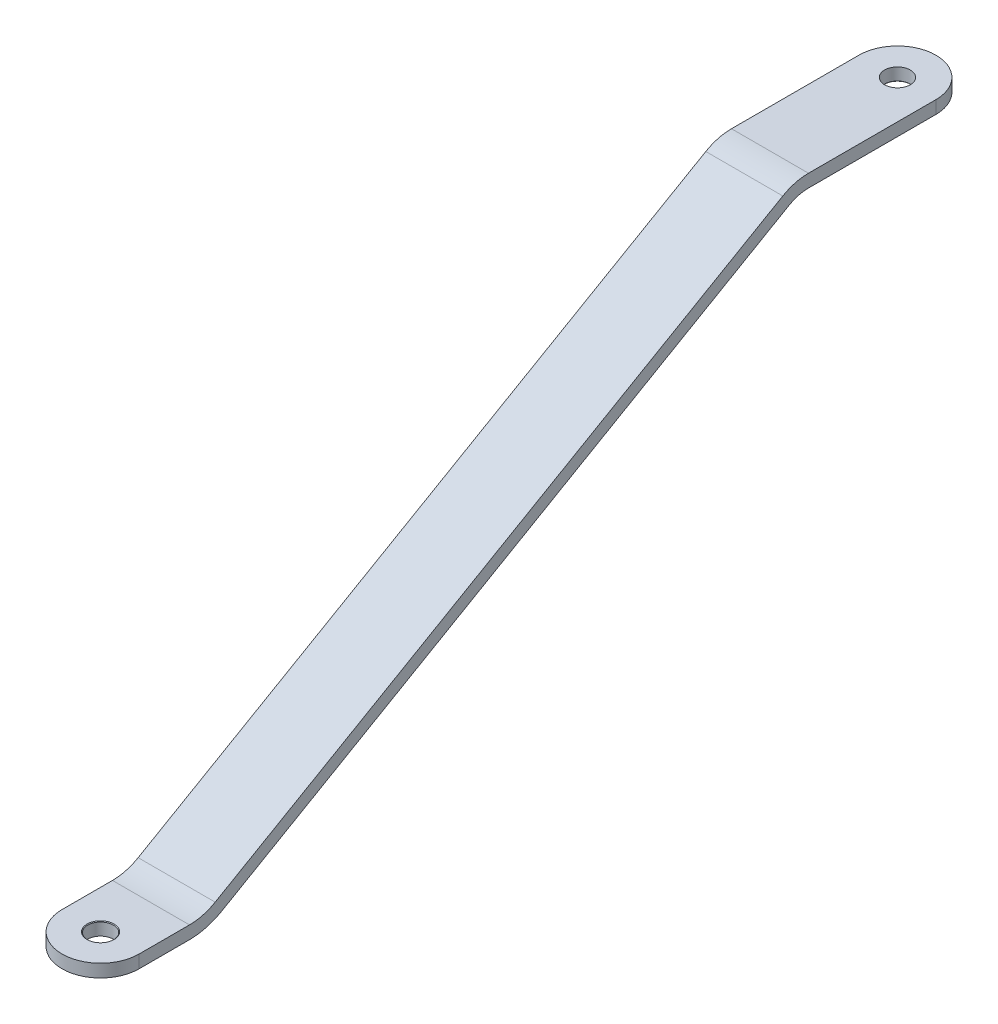
SolidWorks part; units mm, degrees
ref_plane "Front Plane" through (0, 0, 0) normal (0, 0, 1) x (1, 0, 0)
ref_plane "Top Plane" through (0, 0, 0) normal (0, 1, 0) x (1, 0, 0)
ref_plane "Right Plane" through (0, 0, 0) normal (1, 0, 0) x (0, 0, -1)
sketch "Sketch2" plane through (0, 0, 0) normal (1, 0, 0) x (0, 0, -1)
  line L0 (-394.1607, 0) -> (-306.1725, 0)
  line L1 (-280.7725, 6.8059) -> (280.7725, 331.0141)
  line L2 (306.1725, 337.82) -> (470.3607, 337.82)
  line L3 (0, 0) -> (470.3607, 0) construction
  line L4 (-394.1607, -12.7) -> (-306.1725, -12.7)
  line L5 (-274.4225, -4.1926) -> (287.1225, 320.0156)
  line L6 (306.1725, 325.12) -> (470.3607, 325.12)
  line L7 (-394.1607, 0) -> (-394.1607, -12.7)
  line L8 (470.3607, 337.82) -> (470.3607, 325.12)
  arc A0 (280.7725, 331.0141) -> (306.1725, 337.82) centre (306.1725, 287.02) cw
  arc A1 (-306.1725, 0) -> (-280.7725, 6.8059) centre (-306.1725, 50.8) ccw
  arc A2 (-306.1725, -12.7) -> (-274.4225, -4.1926) centre (-306.1725, 50.8) ccw
  arc A3 (287.1225, 320.0156) -> (306.1725, 325.12) centre (306.1725, 287.02) cw
  point P9 (0, 168.91)
  point P14 (292.5607, 337.82)
  point P17 (-292.5607, 0)
  dimension "D5" = 50.8
  dimension "D1" = 101.6
  dimension "D2" = 675.64
  dimension "D3" = 177.8
  dimension "D4" = 30
  dimension "D6" = 12.7
extrude "Boss-Extrude1" add sketch "Sketch2" along normal blind 76.2
fillet "Fillet1" 2 edges at (76.2, -6.35, 394.1607) (0, -6.35, 394.1607) type full round first side face at (76.2, 162.7739, -13.777) second side face at (0, 162.7739, -13.777) middle face at (38.1, -6.35, 394.1607)
fillet "Fillet2" 2 edges at (0, 331.47, -470.3607) (76.2, 331.47, -470.3607) type full round first side face at (0, 162.7739, -20.127) second side face at (76.2, 162.7739, -20.127) middle face at (38.1, 331.47, -470.3607)
hole_wizard "1 (1) Diameter Hole1" positions "Sketch3" profile "Sketch4" hole size "1" standard "ANSI Inch" end condition through all
sketch "Sketch3" plane through (0, 0, 0) normal (0, 1, 0) x (1, 0, 0)
  point P0 (38.1, -356.0607)
sketch "Sketch4" plane through (38.1, 0, 356.0607) normal (1, 0, 0) x (0, 0, 1)
  line L0 (0, 0) -> (0, 12.7)
  line L1 (0, 12.7) -> (12.7, 12.7)
  line L2 (12.7, 12.7) -> (12.7, 0.635)
  line L3 (12.7, 0.635) -> (13.335, 0)
  line L5 (13.335, 0) -> (0, 0)
  line L6 (-12.7, 0.635) -> (-13.335, 0) construction
  line L11 (0, -6.35) -> (0, 107.95) construction
  dimension "Thru Hole Dia." = 25.4
  dimension "Thru Hole Depth" = 12.7
  dimension "Near C'Sink Dia." = 26.67
  dimension "Near C'Sink Angle" = 90
hole_wizard "1 (1) Diameter Hole2" positions "3DSketch1" profile "Sketch7" hole size "1" standard "ANSI Inch" end condition through all
sketch3d "3DSketch1"
  line L0 (38.1, 325.12, -432.2607) -> (38.1, 337.82, -432.2607) construction
  point P0 (38.1, 325.12, -432.2607)
sketch "Sketch7" plane through (38.1, 325.12, -432.2607) normal (1, 0, 0) x (0, 0, -1)
  line L0 (0, 0) -> (0, 12.7)
  line L1 (0, 12.7) -> (12.7, 12.7)
  line L2 (12.7, 12.7) -> (12.7, 0.635)
  line L3 (12.7, 0.635) -> (13.335, 0)
  line L5 (13.335, 0) -> (0, 0)
  line L6 (-12.7, 0.635) -> (-13.335, 0) construction
  line L11 (0, -6.35) -> (0, 107.95) construction
  dimension "Thru Hole Dia." = 25.4
  dimension "Thru Hole Depth" = 12.7
  dimension "Near C'Sink Dia." = 26.67
  dimension "Near C'Sink Angle" = 90
